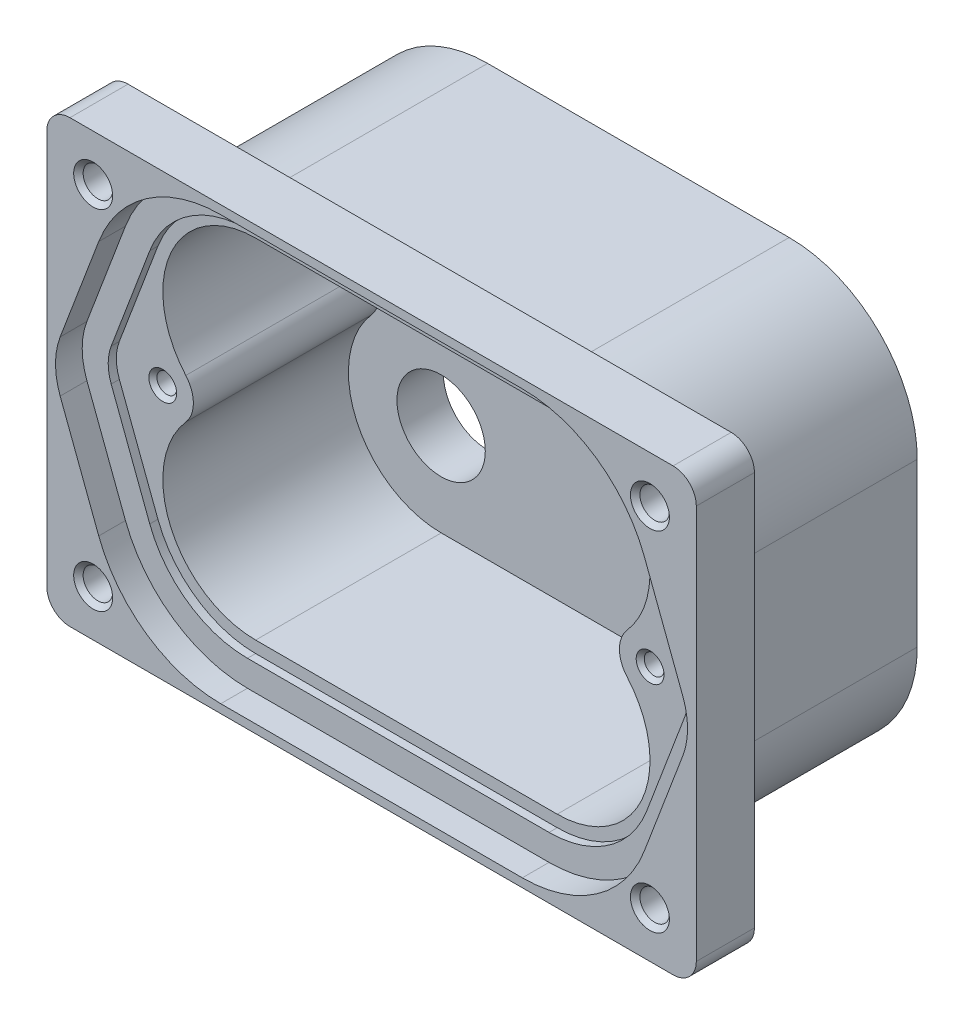
SolidWorks part; units mm, degrees
ref_plane "Front Plane" through (0, 0, 0) normal (0, 0, 1) x (1, 0, 0)
ref_plane "Top Plane" through (0, 0, 0) normal (0, 1, 0) x (1, 0, 0)
ref_plane "Right Plane" through (0, 0, 0) normal (1, 0, 0) x (0, 0, -1)
sketch "Sketch1" plane through (0, 0, 0) normal (0, 0, 1) x (1, 0, 0)
  line L1 (-44.45, 30.1625) -> (44.45, 30.1625)
  line L2 (-44.45, 30.1625) -> (-44.45, -30.1625)
  line L3 (-44.45, -30.1625) -> (44.45, -30.1625)
  line L4 (44.45, 30.1625) -> (44.45, -30.1625)
  point P4 (44.45, 0)
  point P5 (0, 30.1625)
  dimension "D1" = 60.325
  dimension "D2" = 88.9
extrude "Boss-Extrude1" add sketch "Sketch1" against normal blind 36.5252
sketch "Sketch2" plane through (0, 0, 0) normal (0, 0, 1) x (1, 0, 0)
  line L0 (0, 37.303) -> (0, 46.9491) construction
  line L1 (8.6997, 23.8252) -> (20.6375, 23.8252)
  line L3 (8.6997, -23.8252) -> (20.6375, -23.8252)
  line L5 (-8.6997, 23.8252) -> (-20.6375, 23.8252)
  line L6 (-8.6997, -23.8252) -> (-20.6375, -23.8252)
  line L7 (-8.6997, 23.8252) -> (8.6997, 23.8252)
  line L8 (8.6997, -23.8252) -> (-8.6997, -23.8252)
  arc A2 (20.6375, 23.8252) -> (30.1946, 2.7615) centre (20.6375, 11.1252) cw
  arc A3 (20.6375, -23.8252) -> (30.1946, -2.7615) centre (20.6375, -11.1252) ccw
  arc A4 (30.1946, 2.7615) -> (30.1946, -2.7615) centre (33.3502, 0) ccw
  arc A5 (8.6997, 23.8252) -> (2.6785, 20.5202) centre (8.6997, 16.6878) ccw construction
  arc A6 (2.6785, 20.5202) -> (-2.6785, 20.5202) centre (0, 22.225) cw construction
  arc A7 (8.6997, -23.8252) -> (2.6785, -20.5202) centre (8.6997, -16.6878) cw construction
  arc A8 (2.6785, -20.5202) -> (-2.6785, -20.5202) centre (0, -22.225) ccw construction
  arc A9 (-8.6997, 23.8252) -> (-2.6785, 20.5202) centre (-8.6997, 16.6878) cw construction
  arc A10 (-20.6375, 23.8252) -> (-30.1946, 2.7615) centre (-20.6375, 11.1252) ccw
  arc A11 (-30.1946, 2.7615) -> (-30.1946, -2.7615) centre (-33.3502, 0) cw
  arc A12 (-20.6375, -23.8252) -> (-30.1946, -2.7615) centre (-20.6375, -11.1252) cw
  arc A13 (-8.6997, -23.8252) -> (-2.6785, -20.5202) centre (-8.6997, -16.6878) ccw construction
  dimension "D3" = 7.1374
  dimension "D2" = 12.7
  dimension "D1" = 33.3502
  dimension "D6" = 19.05
  dimension "D7" = 3.175
  dimension "D8" = 19.05
  dimension "D4" = 11.1252
  dimension "D5" = 20.6375
extrude "Cut-Extrude1" cut sketch "Sketch2" against normal offset from surface (30.1752 mm away) 6.35 up to face at (0, 0, -36.5252)
sketch "Sketch9" plane through (0, 0, 0) normal (0, 0, 1) x (1, 0, 0)
  line L0 (-20.6375, -25.4254) -> (20.6375, -25.4254)
  line L1 (34.0114, -16.1883) -> (39.2889, -2.2483)
  line L2 (39.2889, 2.2483) -> (34.0114, 16.1883)
  line L3 (20.6375, 25.4254) -> (-20.6375, 25.4254)
  line L4 (0, 10.5861) -> (0, 37.7238) construction
  line L5 (-39.2889, 2.2483) -> (-34.0114, 16.1883)
  line L6 (-34.0114, -16.1883) -> (-39.2889, -2.2483)
  arc A0 (20.6375, -25.4254) -> (34.0114, -16.1883) centre (20.6375, -11.1252) ccw
  arc A1 (39.2889, -2.2483) -> (39.2889, 2.2483) centre (33.3502, 0) ccw
  arc A2 (34.0114, 16.1883) -> (20.6375, 25.4254) centre (20.6375, 11.1252) ccw
  arc A3 (-34.0114, 16.1883) -> (-20.6375, 25.4254) centre (-20.6375, 11.1252) cw
  arc A4 (-39.2889, -2.2483) -> (-39.2889, 2.2483) centre (-33.3502, 0) cw
  arc A5 (-20.6375, -25.4254) -> (-34.0114, -16.1883) centre (-20.6375, -11.1252) cw
  dimension "D1" = 14.3002
  dimension "D2" = 6.35
extrude "Cut-Extrude5" cut sketch "Sketch9" against normal blind 4.7752
sketch "Sketch3" plane through (0, 0, -36.5252) normal (0, 0, -1) x (-1, 0, 0)
  circle A0 centre (-20.6502, 11.1252) radius 6.0452
  circle A1 centre (-20.6502, -11.1252) radius 6.0452
  circle A2 centre (20.6502, 11.1252) radius 6.0452
  circle A3 centre (20.6502, -11.1252) radius 6.0452
  dimension "D1" = 12.0904
  dimension "D2" = 20.6502
  dimension "D3" = 20.6502
  dimension "D4" = 11.1252
  dimension "D5" = 11.1252
extrude "Cut-Extrude2" cut sketch "Sketch3" against normal through all
sketch "Sketch4" plane through (0, 0, 0) normal (0, 0, 1) x (1, 0, 0)
  line L22 (20.6375, 28.9814) -> (-20.6375, 28.9814)
  line L23 (-37.337, 17.4474) -> (-42.6145, 3.5073)
  line L24 (-42.6145, -3.5073) -> (-37.337, -17.4474)
  line L25 (-20.6375, -28.9814) -> (20.6375, -28.9814)
  line L26 (37.337, -17.4474) -> (42.6145, -3.5073)
  line L27 (42.6145, 3.5073) -> (37.337, 17.4474)
  line L28 (20.6375, 28.9814) -> (-20.6375, 28.9814)
  line L29 (-37.337, 17.4474) -> (-42.6145, 3.5073)
  line L30 (-42.6145, -3.5073) -> (-37.337, -17.4474)
  line L31 (-20.6375, -28.9814) -> (20.6375, -28.9814)
  line L32 (37.337, -17.4474) -> (42.6145, -3.5073)
  line L33 (42.6145, 3.5073) -> (37.337, 17.4474)
  arc A18 (-20.6375, 28.9814) -> (-37.337, 17.4474) centre (-20.6375, 11.1252) ccw
  arc A19 (-42.6145, 3.5073) -> (-42.6145, -3.5073) centre (-33.3502, 0) ccw
  arc A20 (-37.337, -17.4474) -> (-20.6375, -28.9814) centre (-20.6375, -11.1252) ccw
  arc A21 (20.6375, -28.9814) -> (37.337, -17.4474) centre (20.6375, -11.1252) ccw
  arc A22 (42.6145, -3.5073) -> (42.6145, 3.5073) centre (33.3502, 0) ccw
  arc A23 (37.337, 17.4474) -> (20.6375, 28.9814) centre (20.6375, 11.1252) ccw
  arc A24 (-20.6375, 28.9814) -> (-37.337, 17.4474) centre (-20.6375, 11.1252) ccw
  arc A25 (-42.6145, 3.5073) -> (-42.6145, -3.5073) centre (-33.3502, 0) ccw
  arc A26 (-37.337, -17.4474) -> (-20.6375, -28.9814) centre (-20.6375, -11.1252) ccw
  arc A27 (20.6375, -28.9814) -> (37.337, -17.4474) centre (20.6375, -11.1252) ccw
  arc A28 (42.6145, -3.5073) -> (42.6145, 3.5073) centre (33.3502, 0) ccw
  arc A29 (37.337, 17.4474) -> (20.6375, 28.9814) centre (20.6375, 11.1252) ccw
  dimension "D1" = 3.556
extrude "Cut-Extrude3" cut sketch "Sketch4" against normal blind 3.6576
sketch "Sketch8" plane through (0, 0, -36.5252) normal (0, 0, -1) x (-1, 0, 0)
  line L0 (20.6375, -28.6512) -> (-20.6375, -28.6512)
  line L1 (-38.1635, -11.1252) -> (-38.1635, 11.1252)
  line L2 (-20.6375, 28.6512) -> (20.6375, 28.6512)
  line L3 (38.1635, 11.1252) -> (38.1635, -11.1252)
  arc A0 (20.6375, 28.6512) -> (38.1635, 11.1252) centre (20.6375, 11.1252) cw
  arc A1 (-38.1635, 11.1252) -> (-20.6375, 28.6512) centre (-20.6375, 11.1252) cw
  arc A2 (-20.6375, -28.6512) -> (-38.1635, -11.1252) centre (-20.6375, -11.1252) cw
  arc A3 (38.1635, -11.1252) -> (20.6375, -28.6512) centre (20.6375, -11.1252) cw
  dimension "D1" = 17.526
extrude "Cut-Extrude4" cut sketch "Sketch8" against normal offset from surface (28.575 mm away) 7.9502 flip side to cut up to face at (0, 0, 0)
hole_wizard "#10-32 Tapped Hole1" positions "Sketch7" profile "Sketch6" tap size "#10-32" standard "Ansi Inch" end condition up to next
sketch "Sketch7" plane through (0, 0, 0) normal (0, 0, 1) x (1, 0, 0)
  point P0 (38.1, 23.8252)
  point P1 (38.1, -23.8252)
  point P3 (-38.1, 23.8252)
  point P5 (-38.1, -23.8252)
  dimension "D1" = 38.1
  dimension "D2" = 23.8252
  dimension "D3" = 23.8252
  dimension "D4" = 38.1
sketch "Sketch6" plane through (38.1, 23.8252, 0) normal (1, 0, 0) x (0, -1, 0)
  line L0 (0, 0) -> (0, 7.9502)
  line L1 (0, 7.9502) -> (2.667, 7.9502)
  line L2 (2.0193, 7.3025) -> (2.0193, 0.6477)
  line L3 (2.0193, 0.6477) -> (2.667, 0)
  line L5 (2.667, 0) -> (0, 0)
  line L6 (-2.0193, 0.6477) -> (-2.667, 0) construction
  line L7 (2.667, 7.9502) -> (2.0193, 7.3025)
  line L8 (-2.667, 7.9502) -> (-2.0193, 7.3025) construction
  line L11 (0, -6.35) -> (0, 107.95) construction
  dimension "Thread Major Dia." = 4.0386
  dimension "Thru Tap Drill Depth" = 7.9502
  dimension "Near C'Sink Dia." = 5.334
  dimension "Near C'Sink Angle" = 90
  dimension "Far C'Sink Dia." = 5.334
  dimension "Far C'Sink Angle" = 90
sketch "Sketch10" plane through (0, 0, 0) normal (0, 0, 1) x (1, 0, 0)
  line L0 (35.6488, 11.7104) -> (28.8483, 2.3249)
  line L1 (2.6424, 23.1953) -> (4.995, 26.727)
  line L2 (4.995, 26.727) -> (-4.995, 26.727)
  line L3 (-4.995, 26.727) -> (-2.6424, 23.1953)
  line L4 (28.8209, -2.2865) -> (35.4794, -11.7104)
  line L5 (35.4794, -11.7104) -> (35.6488, 11.7104)
  arc A0 (-2.6424, 23.1953) -> (2.6424, 23.1953) centre (0, 24.9555) ccw
  arc A1 (28.8483, 2.3249) -> (28.8209, -2.2865) centre (32.057, 0) ccw
  point P0 (0, 26.727)
  point P10 (35.5641, 0)
  dimension "D2" = 3.175
  dimension "D3" = 3.9624
  dimension "D4" = 23.4208
extrude "Boss-Extrude2" [suppressed] add sketch "Sketch10" against normal up to next from offset 4.7752 offset against normal yes
hole_wizard "#6-32 Tapped Hole1" positions "Sketch13" profile "Sketch12" tap size "#6-32" standard "Ansi Inch"
sketch "Sketch13" plane through (0, 0, -4.7752) normal (0, 0, 1) x (1, 0, 0)
  point P0 (33.3502, 0)
  point P1 (-33.3502, 0)
sketch "Sketch12" plane through (33.3502, 0, -4.7752) normal (1, 0, 0) x (0, -1, 0)
  line L0 (0, 0) -> (0, 10.2107)
  line L1 (0, 10.2107) -> (1.3525, 9.398)
  line L2 (1.3525, 9.398) -> (1.3525, 0.5524)
  line L3 (1.3525, 0.5524) -> (1.905, 0)
  line L5 (1.905, 0) -> (0, 0)
  line L6 (-1.3525, 0.5524) -> (-1.905, 0) construction
  line L10 (0, 10.2107) -> (-1.3526, 9.398) construction
  line L11 (0, -6.35) -> (0, 107.95) construction
  dimension "Tap Drill Dia." = 2.7051
  dimension "Tap Drill Depth" = 9.398
  dimension "Near C'Sink Dia." = 3.81
  dimension "Near C'Sink Angle" = 90
  dimension "Drill Angle" = 118
fillet "Fillet1" radius 3.175 4 edges at (44.45, 30.1625, -3.9751) (44.45, -30.1625, -3.9751) (-44.45, 30.1625, -3.9751) (-44.45, -30.1625, -3.9751)
hole_wizard "#8-32 Tapped Hole1" positions "Sketch15" profile "Sketch14" tap size "#8-32" standard "ANSI Inch" end condition up to next
sketch "Sketch15" plane through (0, 0, -30.1752) normal (0, 0, 1) x (1, 0, 0)
  point P0 (-6.35, 15.875)
  point P3 (3.175, 15.875)
  dimension "D1" = 6.35
  dimension "D2" = 15.875
  dimension "D3" = 3.175
sketch "Sketch14" plane through (-6.35, 15.875, -30.1752) normal (1, 0, 0) x (0, -1, 0)
  line L0 (0, 0) -> (0, 6.35)
  line L1 (0, 6.35) -> (2.286, 6.35)
  line L2 (1.7272, 5.7912) -> (1.7272, 0.5588)
  line L3 (1.7272, 0.5588) -> (2.286, 0)
  line L5 (2.286, 0) -> (0, 0)
  line L6 (-1.7272, 0.5588) -> (-2.286, 0) construction
  line L7 (2.286, 6.35) -> (1.7272, 5.7912)
  line L8 (-2.286, 6.35) -> (-1.7272, 5.7912) construction
  line L11 (0, -6.35) -> (0, 107.95) construction
  dimension "Thread Major Dia." = 3.4544
  dimension "Thru Tap Drill Depth" = 6.35
  dimension "Near C'Sink Dia." = 4.572
  dimension "Near C'Sink Angle" = 90
  dimension "Far C'Sink Dia." = 4.572
  dimension "Far C'Sink Angle" = 90
